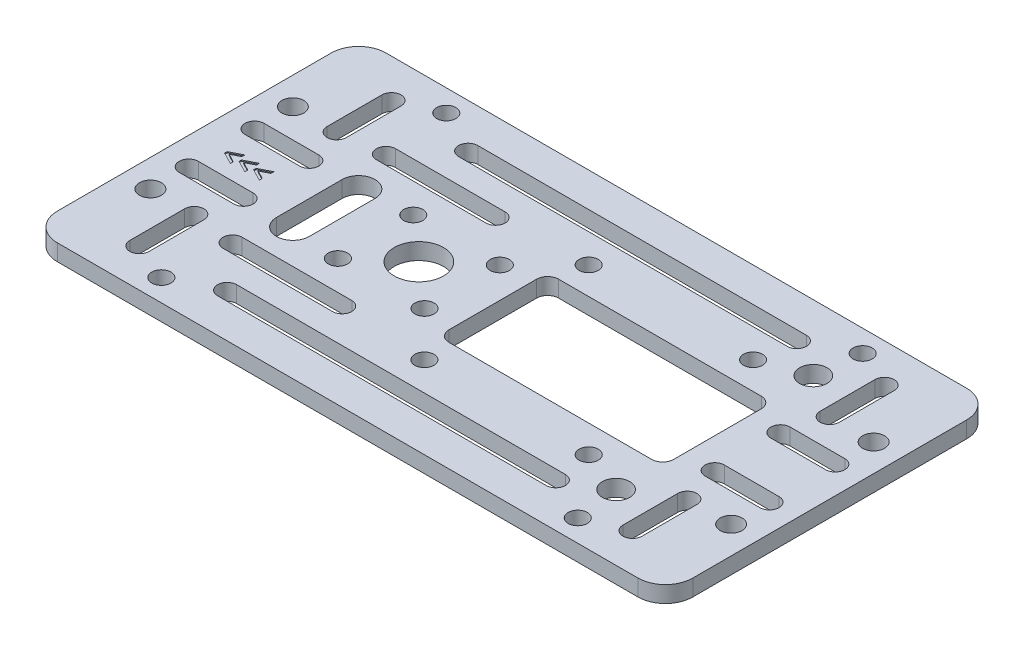
SolidWorks part; units mm, degrees
ref_plane "Front Plane" through (0, 0, 0) normal (0, 0, 1) x (1, 0, 0)
ref_plane "Top Plane" through (0, 0, 0) normal (0, 1, 0) x (1, 0, 0)
ref_plane "Right Plane" through (0, 0, 0) normal (1, 0, 0) x (0, 0, -1)
sketch "Sketch1" plane through (0, 0, 0) normal (0, 1, 0) x (1, 0, 0)
  line L0 (-58, 0) -> (58, 0) construction
  line L1 (-58, 30) -> (58, 30)
  line L2 (-58, 30) -> (-58, -30)
  line L3 (-58, -30) -> (58, -30)
  line L4 (58, 30) -> (58, -30)
  line L5 (-58, 30) -> (58, -30) construction
  line L6 (-58, -30) -> (58, 30) construction
  line L7 (0, 30) -> (0, -30) construction
  circle A0 centre (53, 13) radius 2
  circle A1 centre (53, -13) radius 2
  circle A2 centre (-53, -13) radius 2
  circle A3 centre (-53, 13) radius 2
  point P0 (0, 0)
  dimension "D4" = 4
  dimension "D1" = 60
  dimension "D2" = 116
  dimension "D3" = 13
  dimension "D5" = 53
extrude "Boss-Extrude1" add sketch "Sketch1" along normal blind 3
sketch "Sketch2" plane through (0, 3, 0) normal (0, 1, 0) x (1, 0, 0)
  line L0 (-58, 0) -> (58, 0) construction
  line L1 (-58, 30) -> (-58, -30) construction
  line L2 (58, -30) -> (58, 30) construction
  line L3 (0, 30) -> (0, -30) construction
  line L4 (58, 30) -> (-58, 30) construction
  line L5 (-58, -30) -> (58, -30) construction
  circle A0 centre (38, 26) radius 1.75
  circle A1 centre (38, -26) radius 1.75
  circle A2 centre (-38, -26) radius 1.75
  circle A3 centre (-38, 26) radius 1.75
  dimension "D1" = 3.5
  dimension "D2" = 26
  dimension "D3" = 38
extrude "Odroid-holes" cut sketch "Sketch2" against normal through all
sketch "Sketch3" plane through (0, 3, 0) normal (0, 1, 0) x (1, 0, 0)
  text T0 "<b><<<</b>"
extrude "Cut-Extrude2" cut sketch "Sketch3" against normal blind 0.2
sketch "Sketch4" plane through (0, 3, 0) normal (0, 1, 0) x (1, 0, 0)
  line L0 (58, 0) -> (-58, 0) construction
  line L1 (58, -30) -> (58, 30) construction
  line L2 (-58, 30) -> (-58, -30) construction
  line L3 (14, 30) -> (14, -30) construction
  line L4 (58, 30) -> (-58, 30) construction
  line L5 (-58, -30) -> (58, -30) construction
  line L6 (0, 30) -> (0, -30) construction
  circle A0 centre (-1, 15) radius 1.75
  circle A1 centre (29, 15) radius 1.75
  circle A2 centre (29, -15) radius 1.75
  circle A3 centre (-1, -15) radius 1.75
  dimension "D1" = 3.5
  dimension "D2" = 15
  dimension "D3" = 15
  dimension "D4" = 14
extrude "Pixhawk-PM" cut sketch "Sketch4" against normal through all
sketch "Sketch5" plane through (0, 3, 0) normal (0, 1, 0) x (1, 0, 0)
  line L0 (0, 30) -> (0, -30) construction
  line L1 (58, 30) -> (-58, 30) construction
  line L2 (-58, -30) -> (58, -30) construction
  line L3 (-17, 30) -> (-17, -30) construction
  line L4 (-58, 0) -> (58, 0) construction
  line L5 (-58, 30) -> (-58, -30) construction
  line L6 (58, -30) -> (58, 30) construction
  circle A0 centre (-9.1, 6.875) radius 1.75
  circle A1 centre (-24.9, 6.875) radius 1.75
  circle A2 centre (-24.9, -6.875) radius 1.75
  circle A3 centre (-9.1, -6.875) radius 1.75
  dimension "D1" = 3.5
  dimension "D2" = 6.875
  dimension "D3" = 7.9
  dimension "D4" = 17
extrude "BuckConverter-5A" cut sketch "Sketch5" against normal through all
sketch "Sketch6" plane through (0, 3, 0) normal (0, 1, 0) x (1, 0, 0)
  line L0 (-58, 0) -> (58, 0) construction
  line L1 (-58, 30) -> (-58, -30) construction
  line L2 (58, -30) -> (58, 30) construction
  line L3 (0, 30) -> (0, -30) construction
  line L4 (58, 30) -> (-58, 30) construction
  line L5 (-58, -30) -> (58, -30) construction
  line L6 (-30, 22) -> (30, 22) construction
  line L7 (-30, 23.75) -> (30, 23.75)
  line L8 (-30, 20.25) -> (30, 20.25)
  line L9 (-30, -22) -> (30, -22) construction
  line L10 (-30, -23.75) -> (30, -23.75)
  line L11 (-30, -20.25) -> (30, -20.25)
  line L12 (-37, 14) -> (-17, 14) construction
  line L13 (-37, 15.75) -> (-17, 15.75)
  line L14 (-37, 12.25) -> (-17, 12.25)
  line L15 (-37, -14) -> (-17, -14) construction
  line L16 (-37, -15.75) -> (-17, -15.75)
  line L17 (-37, -12.25) -> (-17, -12.25)
  line L18 (-45, 23) -> (-45, 13) construction
  line L19 (-43.25, 23) -> (-43.25, 13)
  line L20 (-46.75, 23) -> (-46.75, 13)
  line L21 (-45, -23) -> (-45, -13) construction
  line L22 (-43.25, -23) -> (-43.25, -13)
  line L23 (-46.75, -23) -> (-46.75, -13)
  line L24 (45, 23) -> (45, 13) construction
  line L25 (43.25, 23) -> (43.25, 13)
  line L26 (46.75, 23) -> (46.75, 13)
  line L27 (45, -23) -> (45, -13) construction
  line L28 (43.25, -23) -> (43.25, -13)
  line L29 (46.75, -23) -> (46.75, -13)
  line L30 (43, 6) -> (53, 6) construction
  line L31 (43, 7.75) -> (53, 7.75)
  line L32 (43, 4.25) -> (53, 4.25)
  line L33 (43, -6) -> (53, -6) construction
  line L34 (43, -7.75) -> (53, -7.75)
  line L35 (43, -4.25) -> (53, -4.25)
  line L36 (43, -6) -> (53, -6) construction
  line L37 (43, -7.75) -> (53, -7.75)
  line L38 (43, -4.25) -> (53, -4.25)
  line L39 (43, 6) -> (53, 6) construction
  line L40 (43, 7.75) -> (53, 7.75)
  line L41 (43, 4.25) -> (53, 4.25)
  line L42 (43, -6) -> (53, -6) construction
  line L43 (43, -7.75) -> (53, -7.75)
  line L44 (43, -4.25) -> (53, -4.25)
  line L45 (43, 6) -> (53, 6) construction
  line L46 (43, 7.75) -> (53, 7.75)
  line L47 (43, 4.25) -> (53, 4.25)
  line L48 (43, 6) -> (53, 6) construction
  line L49 (43, 7.75) -> (53, 7.75)
  line L50 (43, 4.25) -> (53, 4.25)
  line L51 (43, -6) -> (53, -6) construction
  line L52 (43, -7.75) -> (53, -7.75)
  line L53 (43, -4.25) -> (53, -4.25)
  line L54 (-43, 6) -> (-53, 6) construction
  line L55 (-43, 7.75) -> (-53, 7.75)
  line L56 (-43, 4.25) -> (-53, 4.25)
  line L57 (-43, -6) -> (-53, -6) construction
  line L58 (-43, -7.75) -> (-53, -7.75)
  line L59 (-43, -4.25) -> (-53, -4.25)
  line L60 (-43, 6) -> (-53, 6) construction
  line L61 (-43, 7.75) -> (-53, 7.75)
  line L62 (-43, 4.25) -> (-53, 4.25)
  line L63 (-43, -6) -> (-53, -6) construction
  line L64 (-43, -7.75) -> (-53, -7.75)
  line L65 (-43, -4.25) -> (-53, -4.25)
  line L66 (-43, -6) -> (-53, -6) construction
  line L67 (-43, -7.75) -> (-53, -7.75)
  line L68 (-43, -4.25) -> (-53, -4.25)
  line L69 (-43, 6) -> (-53, 6) construction
  line L70 (-43, 7.75) -> (-53, 7.75)
  line L71 (-43, 4.25) -> (-53, 4.25)
  line L72 (-43, -6) -> (-53, -6) construction
  line L73 (-43, -7.75) -> (-53, -7.75)
  line L74 (-43, -4.25) -> (-53, -4.25)
  line L75 (-43, 6) -> (-53, 6) construction
  line L76 (-43, 7.75) -> (-53, 7.75)
  line L77 (-43, 4.25) -> (-53, 4.25)
  line L78 (-24.9, 6.875) -> (-9.1, 6.875) construction
  line L79 (-1.5, 10) -> (35.5, 10)
  line L80 (-3.5, 8) -> (-3.5, -8)
  line L81 (-1.5, -10) -> (35.5, -10)
  line L82 (37.5, 8) -> (37.5, -8)
  line L83 (-3.5, 10) -> (37.5, -10) construction
  line L84 (-3.5, -10) -> (37.5, 10) construction
  line L85 (-9.1, 6.875) -> (-9.1, -6.875) construction
  line L86 (-9.1, -6.875) -> (-24.9, -6.875) construction
  line L87 (-24.9, -6.875) -> (-24.9, 6.875) construction
  line L88 (-17, 6.875) -> (-17, -6.875) construction
  line L89 (-34, 30) -> (-34, -30) construction
  line L90 (-34, 6) -> (-34, -6) construction
  line L91 (-31, 6) -> (-31, -6)
  line L92 (-37, 6) -> (-37, -6)
  arc A0 (-30, 23.75) -> (-30, 20.25) centre (-30, 22) ccw
  arc A1 (30, 20.25) -> (30, 23.75) centre (30, 22) ccw
  arc A2 (-30, -23.75) -> (-30, -20.25) centre (-30, -22) cw
  arc A3 (30, -20.25) -> (30, -23.75) centre (30, -22) cw
  arc A4 (-37, 15.75) -> (-37, 12.25) centre (-37, 14) ccw
  arc A5 (-17, 12.25) -> (-17, 15.75) centre (-17, 14) ccw
  arc A6 (-37, -15.75) -> (-37, -12.25) centre (-37, -14) cw
  arc A7 (-17, -12.25) -> (-17, -15.75) centre (-17, -14) cw
  arc A8 (-43.25, 23) -> (-46.75, 23) centre (-45, 23) ccw
  arc A9 (-46.75, 13) -> (-43.25, 13) centre (-45, 13) ccw
  arc A10 (-43.25, -23) -> (-46.75, -23) centre (-45, -23) cw
  arc A11 (-46.75, -13) -> (-43.25, -13) centre (-45, -13) cw
  arc A12 (43.25, 23) -> (46.75, 23) centre (45, 23) cw
  arc A13 (46.75, 13) -> (43.25, 13) centre (45, 13) cw
  arc A14 (43.25, -23) -> (46.75, -23) centre (45, -23) ccw
  arc A15 (46.75, -13) -> (43.25, -13) centre (45, -13) ccw
  arc A16 (43, 7.75) -> (43, 4.25) centre (43, 6) ccw
  arc A17 (53, 4.25) -> (53, 7.75) centre (53, 6) ccw
  arc A18 (43, -7.75) -> (43, -4.25) centre (43, -6) cw
  arc A19 (53, -4.25) -> (53, -7.75) centre (53, -6) cw
  arc A20 (43, -7.75) -> (43, -4.25) centre (43, -6) cw
  arc A21 (53, -4.25) -> (53, -7.75) centre (53, -6) cw
  arc A22 (43, 7.75) -> (43, 4.25) centre (43, 6) ccw
  arc A23 (53, 4.25) -> (53, 7.75) centre (53, 6) ccw
  arc A24 (43, -7.75) -> (43, -4.25) centre (43, -6) cw
  arc A25 (53, -4.25) -> (53, -7.75) centre (53, -6) cw
  arc A26 (43, 7.75) -> (43, 4.25) centre (43, 6) ccw
  arc A27 (53, 4.25) -> (53, 7.75) centre (53, 6) ccw
  arc A28 (43, 7.75) -> (43, 4.25) centre (43, 6) ccw
  arc A29 (53, 4.25) -> (53, 7.75) centre (53, 6) ccw
  arc A30 (43, -7.75) -> (43, -4.25) centre (43, -6) cw
  arc A31 (53, -4.25) -> (53, -7.75) centre (53, -6) cw
  arc A32 (-43, 7.75) -> (-43, 4.25) centre (-43, 6) cw
  arc A33 (-53, 4.25) -> (-53, 7.75) centre (-53, 6) cw
  arc A34 (-43, -7.75) -> (-43, -4.25) centre (-43, -6) ccw
  arc A35 (-53, -4.25) -> (-53, -7.75) centre (-53, -6) ccw
  arc A36 (-43, 7.75) -> (-43, 4.25) centre (-43, 6) cw
  arc A37 (-53, 4.25) -> (-53, 7.75) centre (-53, 6) cw
  arc A38 (-43, -7.75) -> (-43, -4.25) centre (-43, -6) ccw
  arc A39 (-53, -4.25) -> (-53, -7.75) centre (-53, -6) ccw
  arc A40 (-43, -7.75) -> (-43, -4.25) centre (-43, -6) ccw
  arc A41 (-53, -4.25) -> (-53, -7.75) centre (-53, -6) ccw
  arc A42 (-43, 7.75) -> (-43, 4.25) centre (-43, 6) cw
  arc A43 (-53, 4.25) -> (-53, 7.75) centre (-53, 6) cw
  arc A44 (-43, -7.75) -> (-43, -4.25) centre (-43, -6) ccw
  arc A45 (-53, -4.25) -> (-53, -7.75) centre (-53, -6) ccw
  arc A46 (-43, 7.75) -> (-43, 4.25) centre (-43, 6) cw
  arc A47 (-53, 4.25) -> (-53, 7.75) centre (-53, 6) cw
  arc A48 (35.5, -10) -> (37.5, -8) centre (35.5, -8) ccw
  arc A49 (35.5, 10) -> (37.5, 8) centre (35.5, 8) cw
  arc A50 (-3.5, -8) -> (-1.5, -10) centre (-1.5, -8) ccw
  arc A51 (-1.5, 10) -> (-3.5, 8) centre (-1.5, 8) ccw
  circle A52 centre (37, 18) radius 2.5
  circle A53 centre (37, -18) radius 2.5
  circle A54 centre (-17, 0) radius 4.5
  arc A55 (-31, 6) -> (-37, 6) centre (-34, 6) ccw
  arc A56 (-37, -6) -> (-31, -6) centre (-34, -6) ccw
  point P14 (0, 22)
  point P21 (0, -22)
  point P28 (-27, 14)
  point P36 (-27, -14)
  point P42 (-45, 18)
  point P49 (-45, -18)
  point P56 (45, 18)
  point P63 (45, -18)
  point P70 (48, 6)
  point P77 (48, -6)
  point P120 (-48, 6)
  point P127 (-48, -6)
  point P168 (17, 0)
  point P205 (-34, 0)
  dimension "D19" = 2
  dimension "D20" = 5
  dimension "D23" = 9
  dimension "D25" = 3
  dimension "D1" = 22
  dimension "D2" = 3.5
  dimension "D3" = 60
  dimension "D4" = 27
  dimension "D5" = 3.5
  dimension "D6" = 20
  dimension "D7" = 14
  dimension "D8" = 18
  dimension "D9" = 45
  dimension "D10" = 10
  dimension "D11" = 3.5
  dimension "D12" = 3.5
  dimension "D13" = 6
  dimension "D14" = 10
  dimension "D15" = 10
  dimension "D16" = 17
  dimension "D17" = 41
  dimension "D18" = 20
  dimension "D21" = 21
  dimension "D22" = 12
  dimension "D24" = 24
  dimension "D26" = 12
extrude "Cut-Extrude5" cut sketch "Sketch6" against normal through all contours L82 L79 L80 L81 | L29 A15 L28 A14 | A54 | L7 A1 L8 A0 | L19 A9 L20 A8 | L13 A5 L14 A4 | L55 A33 L56 A32 | L59 A35 L58 A34 | L17 A7 L16 A6 | L22 A11 L23 A10 | L11 A3 L10 A2 | L35 A19 L34 A18 | L32 A17 L31 A16 | L26 A13 L25 A12 | A52 | A53 | L91 A56 L92 A55 region at (45, 3, 18) region at (17, 3, 0) region at (-17, 3, 0)
fillet "Fillet1" radius 5 4 edges at (58, 1.5, -30) (58, 1.5, 30) (-58, 1.5, 30) (-58, 1.5, -30)
